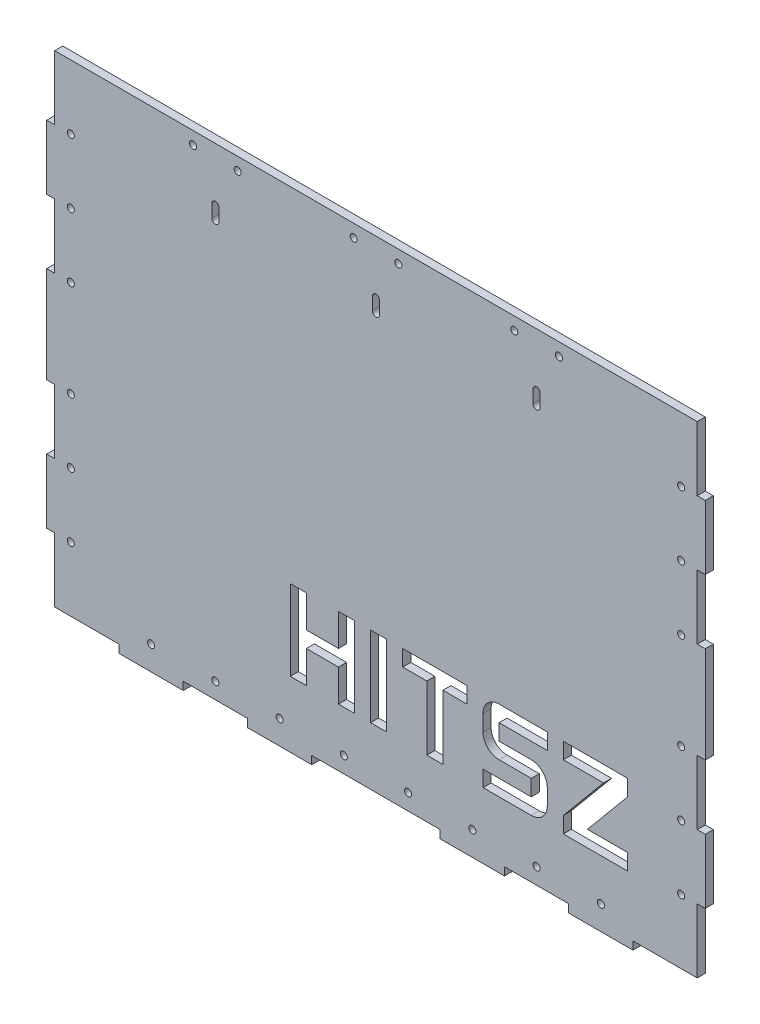
SolidWorks part; units mm, degrees
ref_plane "前视基准面" through (0, 0, 0) normal (0, 0, 1) x (1, 0, 0)
ref_plane "上视基准面" through (0, 0, 0) normal (0, 1, 0) x (1, 0, 0)
ref_plane "右视基准面" through (0, 0, 0) normal (1, 0, 0) x (0, 0, -1)
sketch "草图1" plane through (0, 0, 0) normal (0, 0, 1) x (1, 0, 0)
  line L2 (-200, 150) -> (200, 150)
  line L3 (200, -150) -> (200, -110)
  line L4 (-200, -150) -> (-200, -110)
  line L5 (-200, -150) -> (-160, -150)
  line L6 (-200, -150) -> (-160, -150)
  line L7 (-160, -150) -> (-160, -155)
  line L8 (-160, -155) -> (-120, -155)
  line L9 (-120, -155) -> (-120, -150)
  line L10 (-120, -150) -> (-80, -150)
  line L11 (-80, -150) -> (-80, -155)
  line L12 (-80, -155) -> (-40, -155)
  line L13 (-40, -155) -> (-40, -150)
  line L14 (-40, -150) -> (40, -150)
  line L15 (40, -150) -> (40, -155)
  line L16 (40, -155) -> (80, -155)
  line L17 (80, -155) -> (80, -150)
  line L18 (80, -150) -> (120, -150)
  line L19 (120, -150) -> (120, -155)
  line L20 (120, -155) -> (160, -155)
  line L21 (160, -155) -> (160, -150)
  line L22 (80, -150) -> (120, -150)
  line L23 (-120, -150) -> (-80, -150)
  line L24 (-40, -150) -> (40, -150)
  line L25 (160, -150) -> (200, -150)
  line L26 (-200, 110) -> (-200, 150)
  line L27 (-200, -70) -> (-200, -30)
  line L28 (-205, -30) -> (-205, 30)
  line L29 (-205, 30) -> (-200, 30)
  line L30 (-200, 30) -> (-200, 70)
  line L31 (-200, 70) -> (-205, 70)
  line L32 (-205, 70) -> (-205, 110)
  line L33 (-205, 110) -> (-200, 110)
  line L34 (-205, -30) -> (-200, -30)
  line L35 (-200, -70) -> (-205, -70)
  line L36 (-205, -70) -> (-205, -110)
  line L37 (-205, -110) -> (-200, -110)
  line L38 (-200, 30) -> (-200, 70)
  line L39 (200, 110) -> (200, 150)
  line L40 (205, -70) -> (205, -110)
  line L41 (205, -110) -> (200, -110)
  line L42 (200, -70) -> (205, -70)
  line L43 (205, -30) -> (200, -30)
  line L44 (205, -30) -> (205, 30)
  line L45 (205, 30) -> (200, 30)
  line L46 (200, 70) -> (205, 70)
  line L47 (205, 70) -> (205, 110)
  line L48 (205, 110) -> (200, 110)
  line L49 (200, 30) -> (200, 70)
  line L50 (200, -70) -> (200, -30)
  circle A0 centre (-140, -140) radius 2.2
  circle A1 centre (-100, -140) radius 2.2
  circle A2 centre (-60, -140) radius 2.2
  circle A3 centre (-20, -140) radius 2.2
  circle A4 centre (20, -140) radius 2.2
  circle A5 centre (60, -140) radius 2.2
  circle A6 centre (100, -140) radius 2.2
  circle A7 centre (140, -140) radius 2.2
  circle A8 centre (-190, 110) radius 2.2
  circle A9 centre (-190, 70) radius 2.2
  circle A10 centre (-190, 30) radius 2.2
  circle A11 centre (-190, -30) radius 2.2
  circle A12 centre (-190, -70) radius 2.2
  circle A13 centre (-190, -110) radius 2.2
  circle A14 centre (190, -110) radius 2.2
  circle A15 centre (190, -70) radius 2.2
  circle A16 centre (190, -30) radius 2.2
  circle A17 centre (190, 30) radius 2.2
  circle A18 centre (190, 70) radius 2.2
  circle A19 centre (190, 110) radius 2.2
extrude "凸台-拉伸1" add sketch "草图1" along normal blind 5 contours L42 L50 L43 L44 L45 L49 L46 L47 L48 L39 L2 L26 L33 L32 L31 L30 L29 L28 L34 L27 L35 L36 L37 L4 L5 L7 L8 L9 L10 L11 L12 L13 L14 L15 L16 L17 L18 L19 L20 L21 L25 L3 L41 L40 A18 A16 A14 region at (0, -0.8611, 0)
sketch "草图2" plane through (0, 0, 5) normal (0, 0, 1) x (1, 0, 0)
  line L0 (-23.3543, -114.0171) -> (-13.3543, -114.0171)
  line L1 (-53.3543, -64.0171) -> (-53.3543, -114.0171)
  line L2 (-53.3543, -64.0171) -> (-43.3543, -64.0171)
  line L3 (-43.3543, -64.0171) -> (-43.3543, -84.0171)
  line L4 (-43.3543, -84.0171) -> (-23.3543, -84.0171)
  line L5 (-23.3543, -94.0171) -> (-43.3543, -94.0171)
  line L6 (-43.3543, -94.0171) -> (-43.3543, -114.0171)
  line L7 (-43.3543, -114.0171) -> (-53.3543, -114.0171)
  line L8 (-23.3543, -94.0171) -> (-23.3543, -114.0171)
  line L9 (-23.3543, -64.0171) -> (-23.3543, -84.0171)
  line L10 (-13.3543, -64.0171) -> (-23.3543, -64.0171)
  line L11 (-13.3543, -64.0171) -> (-13.3543, -114.0171)
  line L12 (-3.3543, -64.0171) -> (-3.3543, -114.0171)
  line L13 (-3.3543, -114.0171) -> (6.6457, -114.0171)
  line L14 (6.6457, -114.0171) -> (6.6457, -64.0171)
  line L15 (6.6457, -64.0171) -> (-3.3543, -64.0171)
  line L16 (16.6457, -64.0171) -> (16.6457, -74.0171)
  line L17 (16.6457, -74.0171) -> (31.6457, -74.0171)
  line L18 (31.6457, -74.0171) -> (31.6457, -114.0171)
  line L19 (31.6457, -114.0171) -> (41.6457, -114.0171)
  line L20 (41.6457, -114.0171) -> (41.6457, -74.0171)
  line L21 (41.6457, -74.0171) -> (56.6457, -74.0171)
  line L22 (56.6457, -74.0171) -> (56.6457, -64.0171)
  line L23 (56.6457, -64.0171) -> (16.6457, -64.0171)
  line L24 (66.6457, -74.0171) -> (66.6457, -84.0171)
  line L25 (76.6457, -94.0171) -> (96.6457, -94.0171)
  line L26 (106.6457, -94.0171) -> (106.6457, -104.0171)
  line L27 (96.6457, -114.0171) -> (66.6457, -114.0171)
  line L28 (76.6457, -64.0171) -> (106.6457, -64.0171)
  line L29 (106.6457, -64.0171) -> (106.6457, -74.0171)
  line L30 (76.6457, -84.0171) -> (96.6457, -84.0171)
  line L31 (66.6457, -114.0171) -> (66.6457, -104.0171)
  line L32 (66.6457, -104.0171) -> (96.6457, -104.0171)
  line L33 (106.6457, -74.0171) -> (76.6457, -74.0171)
  line L34 (76.6457, -84.0171) -> (76.6457, -74.0171)
  line L35 (96.6457, -94.0171) -> (96.6457, -104.0171)
  line L37 (116.6457, -64.0171) -> (116.6457, -74.0171)
  line L38 (116.6457, -74.0171) -> (141.6457, -74.0171)
  line L40 (116.6457, -64.0171) -> (156.6457, -64.0171)
  line L41 (156.6457, -64.0171) -> (156.6457, -74.0171)
  line L42 (116.6457, -104.0171) -> (116.6457, -114.0171)
  line L43 (116.6457, -114.0171) -> (156.6457, -114.0171)
  line L44 (156.6457, -114.0171) -> (156.6457, -104.0171)
  line L45 (156.6457, -104.0171) -> (131.6457, -104.0171)
  line L47 (141.6457, -74.0171) -> (116.6457, -104.0171)
  line L49 (131.6457, -104.0171) -> (156.6457, -74.0171)
  arc A0 (76.6457, -64.0171) -> (66.6457, -74.0171) centre (76.6457, -74.0171) ccw
  arc A1 (66.6457, -84.0171) -> (76.6457, -94.0171) centre (76.6457, -84.0171) ccw
  arc A2 (96.6457, -114.0171) -> (106.6457, -104.0171) centre (96.6457, -104.0171) ccw
  arc A3 (106.6457, -94.0171) -> (96.6457, -84.0171) centre (96.6457, -94.0171) ccw
extrude "切除-拉伸1" cut sketch "草图2" against normal blind 10
sketch "草图3" plane through (0, 0, 5) normal (0, 0, 1) x (1, 0, 0)
  line L3 (100, 116.6) -> (100, 108.6) construction
  line L4 (102.2, 116.6) -> (102.2, 108.6)
  line L5 (97.8, 116.6) -> (97.8, 108.6)
  line L6 (-100, 116.6) -> (-100, 108.6) construction
  line L7 (0, 116.6) -> (0, 108.6) construction
  line L8 (2.2, 116.6) -> (2.2, 108.6)
  line L9 (-2.2, 116.6) -> (-2.2, 108.6)
  line L10 (-102.2, 116.6) -> (-102.2, 108.6)
  line L11 (-97.8, 116.6) -> (-97.8, 108.6)
  circle A0 centre (-13.9, 142.1) radius 2.2
  circle A1 centre (13.9, 142.1) radius 2.2
  arc A3 (2.2, 116.6) -> (-2.2, 116.6) centre (0, 116.6) ccw
  arc A4 (-2.2, 108.6) -> (2.2, 108.6) centre (0, 108.6) ccw
  circle A5 centre (86.1, 142.1) radius 2.2
  circle A6 centre (113.9, 142.1) radius 2.2
  arc A7 (102.2, 116.6) -> (97.8, 116.6) centre (100, 116.6) ccw
  arc A8 (97.8, 108.6) -> (102.2, 108.6) centre (100, 108.6) ccw
  arc A9 (-102.2, 116.6) -> (-97.8, 116.6) centre (-100, 116.6) cw
  arc A10 (-97.8, 108.6) -> (-102.2, 108.6) centre (-100, 108.6) cw
  circle A11 centre (-113.9, 142.1) radius 2.2
  circle A12 centre (-86.1, 142.1) radius 2.2
  point P13 (0, 112.6)
  point P25 (100, 112.6)
  point P31 (-100, 112.6)
extrude "切除-拉伸2" cut sketch "草图3" against normal blind 10
